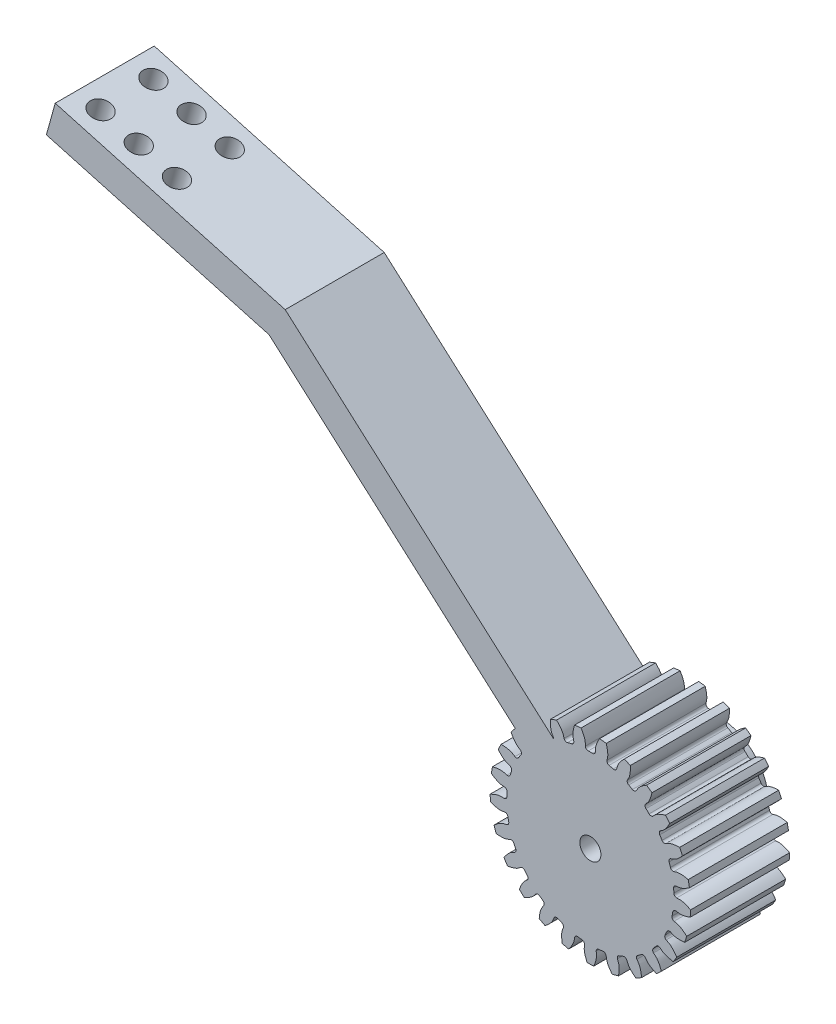
SolidWorks part; units mm, degrees
ref_plane "Front Plane" through (0, 0, 0) normal (0, 0, 1) x (1, 0, 0)
ref_plane "Top Plane" through (0, 0, 0) normal (0, 1, 0) x (1, 0, 0)
ref_plane "Right Plane" through (0, 0, 0) normal (1, 0, 0) x (0, 0, -1)
ref_axis "Axis1" through (0, 0, -88.99) along (0, 0, 1)
sketch "草图1" plane through (0, 0, 0) normal (0, 0, 1) x (1, 0, 0)
  circle A0 centre (0, 0) radius 15.1875
extrude "LaShenA" add sketch "草图1" along normal blind 15
sketch "SketchA" plane through (0, 0, 15) normal (0, 0, 1) x (1, 0, 0)
  line L0 (0, 0) -> (0, 15.1875) construction
  arc A0 (0.3244, 12.6521) -> (-0.3244, 12.6521) centre (0, 0) ccw
  arc A1 (1.842, 15.7559) -> (-1.842, 15.7559) centre (0, 0) ccw
  arc A2 (-0.3244, 12.6521) -> (-0.7617, 13.0474) centre (-0.3354, 13.0795) cw
  arc A3 (0.7617, 13.0474) -> (0.3244, 12.6521) centre (0.3354, 13.0795) cw
  circle A4 centre (0, 0) radius 13.6146 construction
  circle A5 centre (0, 0) radius 15.1875 construction
  circle A6 centre (0, 0) radius 12.6562 construction
  circle A7 centre (0, 0) radius 14.0625 construction
  spline S0 degree 3 poles (0.7617, 13.0474) (0.7753, 13.2289) (0.7594, 13.4417) (0.7888, 13.6649) (0.7997, 13.7227) (0.8093, 13.7685) (0.8217, 13.8211) (0.837, 13.8804) (0.8557, 13.9462) (0.878, 14.0185) (0.9042, 14.097) (0.9347, 14.1818) (0.9697, 14.2725) (1.0095, 14.369) (1.0545, 14.4712) (1.1048, 14.5789) (1.1608, 14.6918) (1.2227, 14.8098) (1.2907, 14.9327) (1.3653, 15.0601) (1.4465, 15.192) (1.5346, 15.328) (1.6644, 15.5184) (1.7689, 15.6607) (1.842, 15.7559) knots 0.123706 0.123706 0.123706 0.123706 0.284027 0.310496 0.322147 0.335916 0.351803 0.369808 0.389932 0.412174 0.436535 0.463013 0.49161 0.522325 0.555159 0.590111 0.627181 0.666369 0.707676 0.751101 0.796644 0.844306 0.894085 1 1 1 1
  spline S1 degree 3 poles (-0.7617, 13.0474) (-0.7753, 13.2289) (-0.7594, 13.4417) (-0.7888, 13.6649) (-0.7997, 13.7227) (-0.8093, 13.7685) (-0.8217, 13.8211) (-0.837, 13.8804) (-0.8557, 13.9462) (-0.878, 14.0185) (-0.9042, 14.097) (-0.9347, 14.1818) (-0.9697, 14.2725) (-1.0095, 14.369) (-1.0545, 14.4712) (-1.1048, 14.5789) (-1.1608, 14.6918) (-1.2227, 14.8098) (-1.2907, 14.9327) (-1.3653, 15.0601) (-1.4465, 15.192) (-1.5346, 15.328) (-1.6644, 15.5184) (-1.7689, 15.6607) (-1.842, 15.7559) knots 0.123706 0.123706 0.123706 0.123706 0.284027 0.310496 0.322147 0.335916 0.351803 0.369808 0.389932 0.412174 0.436535 0.463013 0.49161 0.522325 0.555159 0.590111 0.627181 0.666369 0.707676 0.751101 0.796644 0.844306 0.894085 1 1 1 1
  dimension "D1" = 0.4275
  dimension "Db" = 27.2292
  dimension "Da" = 30.375
  dimension "Df" = 25.3125
  dimension "Dn" = 28.125
extrude "Cut-ExtrudeA" cut sketch "SketchA" against normal blind 15
pattern_circular "www.KYTool.cn" count 25 over 360 about axis through (0, 0, -88.99) along (0, 0, 1) of "Cut-ExtrudeA"
sketch "草图2" plane through (0, 0, 15) normal (0, 0, 1) x (1, 0, 0)
  circle A0 centre (0, 0) radius 1.6
  dimension "D1" = 3.2
extrude "切除-拉伸1" cut sketch "草图2" against normal blind 19
sketch "草图3" plane through (0, 0, 0) normal (0, 0, -1) x (-1, 0, 0)
  circle A0 centre (0, 0) radius 1.6
  circle A1 centre (0, 0) radius 7.5
  dimension "D1" = 15
  dimension "D2" = 3.2
extrude "凸台-拉伸1" add sketch "草图3" along normal blind 4.5
sketch "草图4" plane through (0, 0, 15) normal (0, 0, 1) x (1, 0, 0)
  line L0 (0, 0) -> (13.8123, -6.0082) construction
  line L1 (-45.1081, 4.2889) -> (-24.7113, -4.5835) construction
sketch "草图6" plane through (0, 0, 15) normal (0, 0, 1) x (1, 0, 0)
  line L0 (-1.3755, 0.5983) -> (-41.669, 18.1255) construction
  line L1 (-45.1081, 4.2889) -> (-24.7113, -4.5835) construction
  line L2 (-1.1233, 0.9941) -> (-48.6758, 43.0775)
  line L3 (-48.6758, 43.0775) -> (-82.4015, 52.4358)
  line L4 (3.3137, 3.7443) -> (-46.2266, 47.5868)
  line L5 (-46.2266, 47.5868) -> (-81.0646, 57.2537)
  line L6 (-81.0646, 57.2537) -> (-82.4015, 52.4358)
  line L7 (3.3137, 3.7443) -> (0.9941, 1.1233)
  line L8 (0, 0) -> (-48.6758, 43.0775) construction
  arc A0 (0.9941, 1.1233) -> (-1.1233, 0.9941) centre (0, 0) ccw
  dimension "D1" = 18
  dimension "D2" = 65
  dimension "D3" = 35
  dimension "D5" = 8
  dimension "D4" = 5
extrude "凸台-拉伸3" add sketch "草图6" against normal up to surface (15 mm away) up to face at (0, 0, 0)
sketch "草图7" plane through (0, 0, 15) normal (0, 0, 1) x (1, 0, 0)
  circle A0 centre (0, 0) radius 1.6
  dimension "D1" = 3.2
extrude "切除-拉伸2" cut sketch "草图7" against normal blind 30
sketch "草图8" plane through (8.9557, 32.2746, 0) normal (0.2674, 0.9636, 0) x (0.9636, -0.2674, 0)
  line L0 (-93.4216, -7.5) -> (-87.536, -7.5) construction
  line L1 (-93.4216, 0) -> (-93.4216, -15) construction
  line L2 (-87.4216, -7.5) -> (-81.536, -7.5) construction
  line L3 (-81.4216, -7.5) -> (-75.536, -7.5) construction
  circle A0 centre (-89.9216, -3.5) radius 1.6
  circle A1 centre (-89.9216, -11.5) radius 1.6
  circle A2 centre (-83.9216, -3.5) radius 1.6
  circle A3 centre (-83.9216, -11.5) radius 1.6
  circle A4 centre (-77.9216, -3.5) radius 1.6
  circle A5 centre (-77.9216, -11.5) radius 1.6
  dimension "D1" = 3.2
  dimension "D2" = 3.5
  dimension "D3" = 4
  dimension "D5" = 6
  dimension "D4" = 3
extrude "切除-拉伸3" cut sketch "草图8" against normal blind 10
